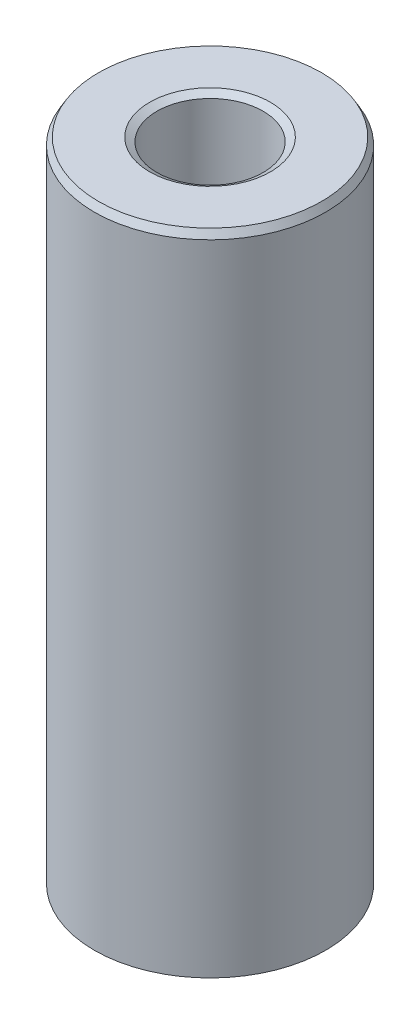
SolidWorks part; units mm, degrees
ref_plane "Front Plane" through (0, 0, 0) normal (0, 0, 1) x (1, 0, 0)
ref_plane "Top Plane" through (0, 0, 0) normal (0, 1, 0) x (1, 0, 0)
ref_plane "Right Plane" through (0, 0, 0) normal (1, 0, 0) x (0, 0, -1)
sketch "Sketch1" plane through (0, 0, 0) normal (0, 1, 0) x (1, 0, 0)
  circle A0 centre (0, 0) radius 52.5
  dimension "SLEEVE_OD" = 105
extrude "Boss-Extrude1" add sketch "Sketch1" along normal blind 295.2009
sketch "Sketch2" plane through (0, 0, 0) normal (0, 1, 0) x (1, 0, 0)
  circle A0 centre (0, 0) radius 24.1138
  dimension "BORE_D" = 48.2275
extrude "Cut-Extrude1" cut sketch "Sketch2" along normal through all
chamfer "Chamfer1" distance 3.2729 angle 30 4 edges at (0, 295.2009, 24.1138) (0, 0, 24.1138) (0, 0, 52.5) (0, 295.2009, 52.5) first distance on face at (0, 295.2009, 24.1138) first distance on face at (0, 0, 24.1138) first distance on face at (0, 295.2009, 52.5)
